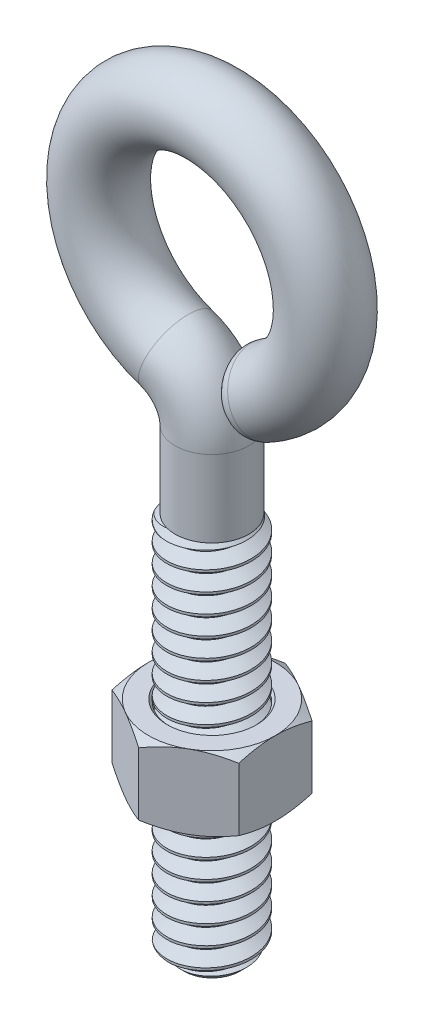
SolidWorks part; units mm, degrees
ref_plane "Front Plane" through (0, 0, 0) normal (0, 0, 1) x (1, 0, 0)
ref_plane "Top Plane" through (0, 0, 0) normal (0, 1, 0) x (1, 0, 0)
ref_plane "Right Plane" through (0, 0, 0) normal (1, 0, 0) x (0, 0, -1)
sketch "Sketch1" plane through (0, 0, 0) normal (0, 0, 1) x (1, 0, 0)
  line L0 (0, -6.477) -> (0, -25.527) construction
  line L1 (-1.7526, -25.527) -> (1.7526, -25.527) construction
  line L2 (0, -9.652) -> (1.7526, -9.652) construction
  line L3 (0, -6.477) -> (0, -3.175) construction
  line L4 (-1.524, -9.652) -> (1.524, -9.652) construction
  line L5 (1.524, -9.652) -> (1.524, -6.477) construction
  line L7 (1.7526, -25.527) -> (1.7526, -9.652) construction
  line L8 (1.524, -6.477) -> (0, -6.477) construction
  circle A0 centre (0, 0) radius 6.223 construction
  circle A1 centre (0, 4.699) radius 1.524 construction
  circle A2 centre (0, 0) radius 3.175 construction
  point P9 (0, -6.477)
  point P10 (0, 6.223)
  point P11 (0, 3.175)
  point P14 (0, -25.527)
  point P24 (0, -9.652)
  dimension "A" = 3.048
  dimension "Eye Dia." = 6.35
  dimension "Shank Lg." = 19.05
  dimension "Thread OD" = 3.5052
  dimension "Thread Lg." = 15.875
  dimension "Overall Lg." = 31.75
  dimension "OD" = 12.7
  dimension "Wire OD." = 3.048
sketch "Sketch2" plane through (0, 0, 0) normal (0, 1, 0) x (1, 0, 0)
  circle A0 centre (0, 0) radius 1.7526
extrude "Boss-Extrude1" add sketch "Sketch2" against normal up to vertex (25.527 mm away) from vertex at -9.652 starting at point (0, -9.652, 0)
sketch "Sketch3" plane through (0, -25.527, 0) normal (0, -1, 0) x (1, 0, 0)
  circle A1 centre (0, 0) radius 1.7526
  circle A2 centre (0, 0) radius 1.7526
  point P0 (1.7526, 0)
  point P1 (0, -1.7526)
  dimension "D1" = 0
curve "Helix/Spiral1" pitch 0.7937 height 16.6687 turns 21 parameters "Pitch"=0.7937
sketch "Sketch4" plane through (0, 0, 0) normal (0, 0, 1) x (1, 0, 0)
  line L0 (1.8385, -25.4774) -> (1.8385, -26.2711) construction
  line L1 (1.8385, -26.2711) -> (1.1511, -25.8743) construction
  line L2 (1.1511, -25.8743) -> (1.8385, -25.4774) construction
  line L3 (1.237, -25.8247) -> (1.237, -25.9239) construction
  line L4 (1.7526, -25.527) -> (1.7526, -26.2215) construction
  line L5 (1.1511, -25.8743) -> (1.237, -25.8743) construction
  line L6 (1.7526, -25.8743) -> (1.8385, -25.8743) construction
  line L7 (1.7956, -25.5022) -> (1.237, -25.8247)
  line L8 (1.237, -25.8247) -> (1.237, -25.9239)
  line L9 (1.237, -25.9239) -> (1.7956, -26.2463)
  line L10 (1.7956, -26.2463) -> (1.7956, -25.5022)
  point P13 (1.7956, -25.8743)
  dimension "D1" = 0.7937
  dimension "D2" = 0.0992
sweep "Cut-Sweep1" cut profiles "Sketch4" path "Helix/Spiral1"
sketch "Sketch5" plane through (0, -25.527, 0) normal (0, -1, 0) x (1, 0, 0)
  circle A0 centre (0, 0) radius 1.1511
extrude "Cut-Extrude1" cut sketch "Sketch5" against normal up to vertex (15.875 mm away) draft 45 flip side to cut up to point (0, -9.652, 0)
sketch "Sketch7" plane through (0, -9.652, 0) normal (0, 1, 0) x (1, 0, 0)
  circle A0 centre (0, 0) radius 1.524
sketch "Sketch8" plane through (0, 0, 0) normal (0, 0, 1) x (1, 0, 0)
  line L0 (0, -6.477) -> (0, -25.527) construction
  line L1 (0, -6.477) -> (0, -9.652)
  line L2 (0, -6.477) -> (0, -3.175) construction
  arc A0 (1.5038, -4.4519) -> (-1.4582, -4.467) centre (0, 0) ccw
  arc A1 (0, -6.477) -> (-1.4582, -4.467) centre (-2.1144, -6.477) ccw
  circle A3 centre (0, -4.699) radius 1.524 construction
sketch "Sketch6" plane through (0, -9.652, 0) normal (0, 1, 0) x (1, 0, 0)
  circle A0 centre (0, 0) radius 1.524
extrude "Cut-Extrude2" cut sketch "Sketch6" against normal up to vertex (15.875 mm away) draft 45 flip side to cut up to point (0, -25.527, 0)
sweep "Sweep1" add profiles "Sketch7" path "Sketch8"
fillet "Fillet1" radius 0.8763 1 edges at (1.5038, -4.4519, 1.524)
sketch "Sketch9" plane through (0, -25.527, 0) normal (0, -1, 0) x (1, 0, 0)
  line L1 (0, 3.0356) -> (-2.6289, 1.5178)
  line L2 (-2.6289, 1.5178) -> (-2.6289, -1.5178)
  line L3 (-2.6289, -1.5178) -> (0, -3.0356)
  line L4 (0, -3.0356) -> (2.6289, -1.5178)
  line L5 (2.6289, -1.5178) -> (2.6289, 1.5178)
  line L6 (2.6289, 1.5178) -> (0, 3.0356)
  circle A0 centre (0, 0) radius 2.6289 construction
  circle A1 centre (0, 0) radius 1.7526
  dimension "Nut Wd." = 5.2578
extrude "Boss-Extrude2" add sketch "Sketch9" against normal blind 3.0671 from offset 6.1341 separate body
sketch "Sketch10" plane through (0, 0, 0) normal (1, 0, 0) x (0, 0, -1)
  line L0 (-2.6289, -16.3258) -> (-3.4423, -16.3258)
  line L1 (-3.4423, -16.3258) -> (-3.4423, -19.3929)
  line L2 (-3.4423, -19.3929) -> (-2.6289, -19.3929)
  line L3 (-2.6289, -19.3929) -> (-3.0356, -19.1581)
  line L4 (-3.0356, -19.1581) -> (-3.0356, -16.5607)
  line L5 (-3.0356, -16.5607) -> (-2.6289, -16.3258)
  line L6 (-1.6534, -16.3258) -> (-1.6534, -19.3929)
  line L7 (-1.6534, -19.3929) -> (-1.8518, -19.3929)
  line L8 (-1.8518, -19.3929) -> (-1.7526, -19.2937)
  line L9 (-1.7526, -19.2937) -> (-1.7526, -16.4251)
  line L10 (-1.7526, -16.4251) -> (-1.8518, -16.3258)
  line L11 (-1.8518, -16.3258) -> (-1.6534, -16.3258)
  line L12 (-1.7526, -16.3258) -> (-1.7526, -19.3929) construction
  line L14 (-1.7526, -19.2937) -> (-1.7526, -19.3929) construction
  line L15 (-1.7526, -16.4251) -> (-1.7526, -16.3258) construction
  line L16 (-3.0356, -16.3258) -> (-3.0356, -19.3929) construction
  line L18 (-2.6289, -19.3929) -> (-2.6289, -25.527) construction
  dimension "D1" = 60
  dimension "D2" = 45
  dimension "D3" = 0.0992
revolve "Cut-Revolve1" cut sketch "Sketch10" angle 360 about L0
sketch "SketchX" plane through (0, 0, 0) normal (1, 0, 0) x (0, 0, -1)
  line L0 (1.7526, -25.527) -> (1.7526, -12.6286) construction
  dimension "D1" = 12.8984
equation "\"D3@Helix/Spiral1\" = \"Pitch@Helix/Spiral1\" + \"Thread Lg.@Sketch1\""
equation "\"D1@Sketch4\" = \"Pitch@Helix/Spiral1\""
equation "\"A@Sketch1\" = \"Wire OD.@Sketch1\""
equation "\"D2@Sketch4\" = \"D1@Sketch4\" / 8"
equation "\"D1@Fillet1\" = \"Thread OD@Sketch1\" / 4"
equation "\"D1@SketchX\" = \"Thread Lg.@Sketch1\" -  ( \"Pitch@Helix/Spiral1\" *  4 ) +  ( \"Pitch@Helix/Spiral1\" /  4 ) "
equation "\"Nut Wd.@Sketch9\" = \"Thread OD@Sketch1\" * 1.5"
equation "\"Nut Ht.@Boss-Extrude2\" = \"Thread OD@Sketch1\" * 0.875"
equation "\"Offset@Boss-Extrude2\" = \"Nut Ht.@Boss-Extrude2\" * 2"
equation "\"D3@Sketch10\" = \"Pitch@Helix/Spiral1\" / 8"
